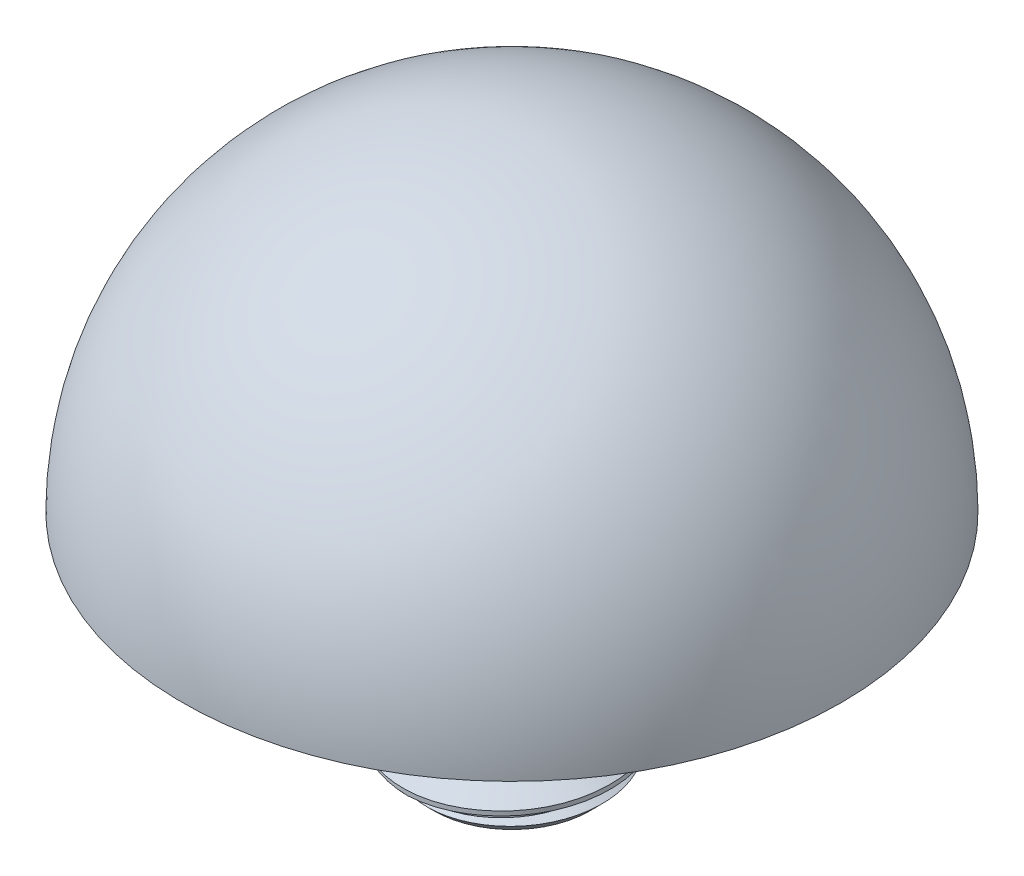
SolidWorks part; units mm, degrees
ref_plane "Front Plane" through (0, 0, 0) normal (0, 0, 1) x (1, 0, 0)
ref_plane "Top Plane" through (0, 0, 0) normal (0, 1, 0) x (1, 0, 0)
ref_plane "Right Plane" through (0, 0, 0) normal (1, 0, 0) x (0, 0, -1)
sketch "Sketch1" plane through (0, 0, 0) normal (0, 0, 1) x (1, 0, 0)
  line L0 (0, 0) -> (0, 9.525) construction
  line L1 (0, 0) -> (0, -6.35) construction
  line L2 (-9.525, 0) -> (9.525, 0) construction
  line L3 (3, -6.35) -> (-3, -6.35) construction
  line L4 (3.1083, -6.2875) -> (2.2422, -6.7875) construction
  line L5 (2.2422, -6.7875) -> (3.1083, -7.2875) construction
  line L6 (3.1083, -7.2875) -> (3.1083, -6.2875) construction
  line L7 (3, -6.35) -> (3, -7.225) construction
  line L8 (3.1083, -6.7875) -> (3, -6.7875) construction
  line L9 (3, -6.7875) -> (2.3505, -6.7875) construction
  line L10 (2.3505, -6.7875) -> (2.2422, -6.7875) construction
  line L11 (2.3505, -6.725) -> (2.3505, -6.85)
  line L12 (3.0541, -6.3188) -> (3.0541, -7.2562)
  line L13 (2.3505, -6.85) -> (3.0541, -7.2562)
  line L14 (2.3505, -6.725) -> (3.0541, -6.3188)
  point P7 (0, 0)
  point P10 (0, -6.35)
  point P22 (3.0541, -6.7875)
  point P24 (3, -4.35)
  dimension "OD" = 19.05
  dimension "Height" = 9.525
  dimension "Thread Length" = 6.35
  dimension "Thread Size" = 6
  dimension "Pitch" = 1
  dimension "D2" = 0.125
  dimension "D1" = 2
sketch "Sketch2" plane through (0, 0, 0) normal (0, 0, 1) x (1, 0, 0)
  line L0 (0, -6.35) -> (0, 9.525)
  line L3 (9.525, 0) -> (3, 0)
  line L4 (-9.525, 0) -> (9.525, 0) construction
  line L5 (3, 0) -> (3, -6.35)
  line L6 (3, -6.35) -> (0, -6.35)
  arc A2 (9.525, 0) -> (0, 9.525) centre (0, 0) ccw
revolve "Revolve1" add sketch "Sketch2" angle 360 about L0
sketch "Sketch3" plane through (0, -6.35, 0) normal (0, -1, 0) x (1, 0, 0)
  circle A0 centre (0, 0) radius 3 construction
  circle A1 centre (0, 0) radius 3
curve "Helix/Spiral1" pitch 1 height 7.35 radius 3 centre (0, -6.35, 0) axis (0, 1, 0) start towards (1, 0, 0) parameters "Pitch"=1
sketch "Sketch4" plane through (0, 0, 0) normal (0, 0, 1) x (1, 0, 0)
  line L4 (2.3505, -6.725) -> (2.3505, -6.85) construction
  line L5 (2.3505, -6.725) -> (3.0541, -6.3188) construction
  line L6 (3.0541, -6.3188) -> (3.0541, -7.2562) construction
  line L7 (2.3505, -6.85) -> (3.0541, -7.2562) construction
  line L8 (2.3505, -6.725) -> (2.3505, -6.85)
  line L9 (2.3505, -6.725) -> (3.0541, -6.3188)
  line L10 (3.0541, -6.3188) -> (3.0541, -7.2562)
  line L11 (2.3505, -6.85) -> (3.0541, -7.2562)
chamfer "Chamfer1" distance 0.75 angle 45 1 edges at (3, -6.35, 0)
sweep "Cut-Sweep1" cut profiles "Sketch4" path "Helix/Spiral1"
equation "\"D3@Helix/Spiral1\"=\"Thread Length@Sketch1\"+\"Pitch@Helix/Spiral1\""
equation "\"D1@Chamfer1\"=\"Pitch@Helix/Spiral1\"*.75"
equation "\"D2@Sketch1\" = \"Pitch@Sketch1\" / 8"
equation "\"D1@Sketch1\"=\"Pitch@Sketch1\"*2"
equation "\"Pitch@Helix/Spiral1\"=\"pitch@sketch1\""
